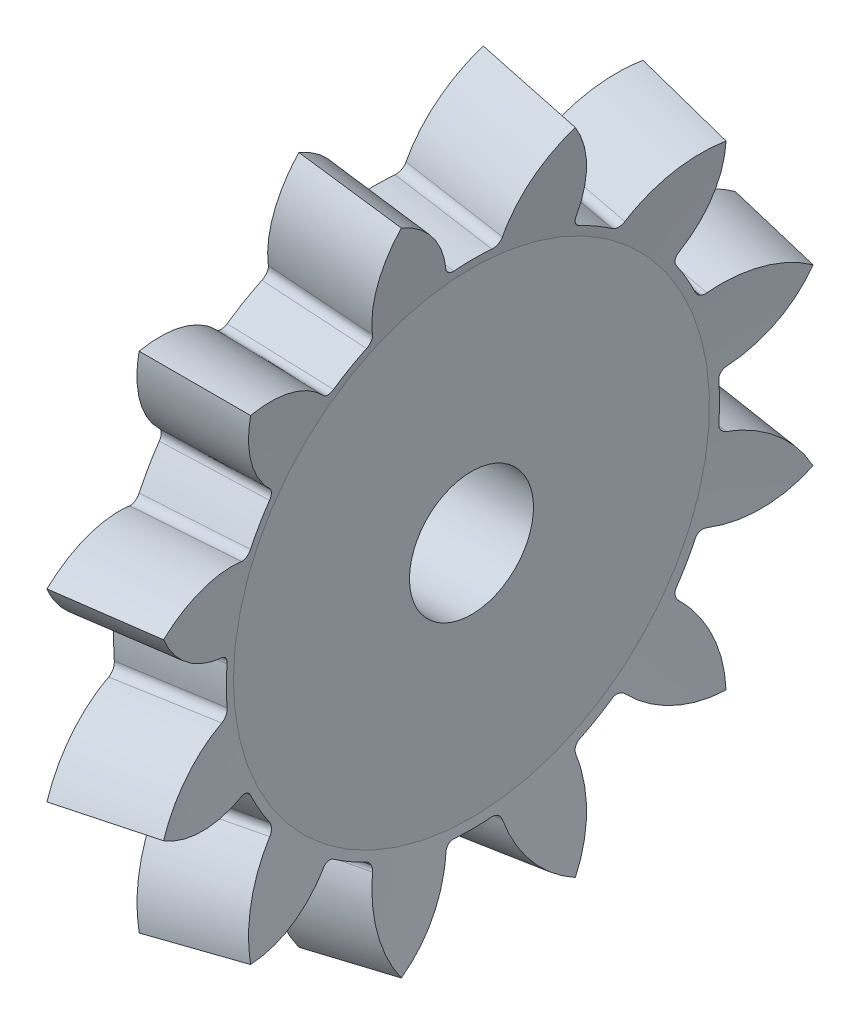
SolidWorks part; units mm, degrees
revolve "Base-Revolve" add sketch "BasProSke" angle 360 about L0 other way angle 15
sketch "BasProSke" plane through (0, 0, 0) normal (0, 1, 0) x (1, 0, 0)
  line L0 (-10, 0) -> (60, 0) construction
  line L1 (0, 0) -> (0, 10.1716)
  line L2 (0, 0) -> (3.9601, 0)
  line L3 (3.9601, 0) -> (3.9601, 9.5987)
  line L4 (70.3134, 0) -> (-30.9402, 17.3578) construction
  line L5 (0, 10.1716) -> (0.8022, 14.8514)
  line L6 (70.3134, 0) -> (-53.9726, 26.5543) construction
  line L7 (70.3134, 0) -> (0, 10.1716) construction
  line L8 (0.8022, 14.8514) -> (4.7172, 14.0149)
  line L9 (4.7172, 14.0149) -> (3.9601, 9.5987)
  line L10 (0.3134, 12) -> (-11.6709, 12) construction
  dimension "Addendum" = 2.893
  dimension "Pitch_rad" = 12
  dimension "Dedendum_plus" = 1.855
  dimension "Face_wid" = 4
  dimension "Pitch_ang" = 9.728
  dimension "D1" = 20.3433
  dimension "D2" = 70.3134
  dimension "D3" = 71.0211
  dimension "D4" = 2.333
ref_plane "Plane1" through (0, 0, 0) normal (0, 0, 1) x (1, 0, 0)
ref_plane "Plane2" through (0, 0, 0) normal (0, 1, 0) x (1, 0, 0)
ref_plane "Plane3" through (0, 0, 0) normal (1, 0, 0) x (0, 0, -1)
sketch "HoldingSke" plane through (0, 0, 0) normal (0, 1, 0) x (1, 0, 0)
  line L0 (0, 0) -> (0.4891, -0.104)
  line L1 (-15, 0) -> (100, 0) construction
  line L2 (0, 0) -> (20.372, 93.3937)
  line L3 (0, 0) -> (-11.863, 4.5341)
  line L4 (0, 0) -> (8.4473, 1.7955)
  line L5 (0, 0) -> (-9.3695, -3.4946)
  line L6 (0, 0) -> (-10.5278, -7.1032)
  line L7 (20.372, 93.3937) -> (80.2793, 130.2054)
  line L8 (-76.2, 2) -> (-75.3, 2)
  line L9 (-71.009, 38.7566) -> (-53.1078, 45.2721)
  line L10 (-76.2, 71.12) -> (104.1128, 71.12)
  line L11 (0, 0) -> (-4, 0)
  line L12 (-76.2, 101.6) -> (-76.133, 101.6)
  line L13 (24.9733, 27.94) -> (52.9472, 28.6464)
  line L14 (24.9733, 27.94) -> (24.9743, 27.94)
  line L15 (24.9733, 27.94) -> (100.4123, 28.9164)
  line L16 (20.372, 93.3937) -> (64.5293, -27.9275)
  circle A0 centre (0, 0) radius 2.5
  circle A1 centre (0, 0) radius 2.5
  circle A2 centre (0, 0) radius 2.5
  circle A3 centre (0, 0) radius 2.5
  dimension "MHD" = 5
  dimension "Hub_dia" = 5
  dimension "Bore" = 5
  dimension "MBD" = 5
  dimension "Num_teeth" = 12
  dimension "Pitch" = 0.5
  dimension "Mounting_dist" = 10
  dimension "Show_teeth" = 12
  dimension "Thickness" = 12.7
  dimension "OAL" = 70.3135
  dimension "T_dim" = 0.9
  dimension "Ap" = 20
  dimension "H" = 19.05
  dimension "Pitch_radius" = 180.3128
  dimension "Width" = 4
  dimension "Backlash" = 0.067
  dimension "Addendum_fac" = 1.446
  dimension "Dedendum_fac" = 0.742
  dimension "Clearance_fac" = 0.188
  dimension "Dedendum_add" = 0.001
  dimension "Mating_teeth" = 70
  dimension "MnMD" = 70.3134
  dimension "Module" = 2
ref_plane "ToothPln" through (0.4011, 12.5115, 0) normal (-0.9856, 0.169, 0) x (0, 0, -1)
ref_plane "ToothPln2" through (68.3061, -11.7096, 0) normal (-0.9856, 0.169, 0) x (0, 0, 1)
sketch "TooCutSke" plane through (0.4011, 12.5115, 0) normal (-0.9856, 0.169, 0) x (0, 0, -1)
  line L2 (0, 12.519) -> (431.6758, -1598.5171) construction
  line L3 (0, 12.519) -> (236.3419, -1744.44) construction
  line L4 (0, -15.621) -> (0, 105.791) construction
  line L6 (-24.765, -2.374) -> (21.082, -2.374) construction
  line L7 (3.1058, 0.9278) -> (1.5867, 0.7235) construction
  arc A0 (-4.9917, -1.8283) -> (4.9917, -1.8283) centre (0, 12.519) ccw
  arc A1 (-0.8122, 2.0344) -> (0.8122, 2.0344) centre (0, 12.519) ccw
  circle A2 centre (0, 12.519) radius 12 construction
  circle A3 centre (0, 12.519) radius 11.2763 construction
  arc A4 (1.2075, 1.7483) -> (0.8122, 2.0344) centre (0.8414, 1.6585) ccw
  arc A5 (1.2075, 1.7483) -> (4.9917, -1.8283) centre (5.8696, 2.8907) ccw
  arc A6 (-4.9917, -1.8283) -> (-1.2075, 1.7483) centre (-5.8696, 2.8907) ccw
  arc A7 (-0.8122, 2.0344) -> (-1.2075, 1.7483) centre (-0.8414, 1.6585) ccw
  ellipse E0 centre (0, 12.2638) end of major axis (14.8514, 12.2638) minor radius 14.6378 construction
sketch "TooCutSke2" plane through (68.3061, -11.7096, 0) normal (-0.9856, 0.169, 0) x (0, 0, 1)
  line L0 (0, 0) -> (0, 68.072) construction
  line L2 (21.082, 10.0254) -> (-20.32, 10.0254) construction
  circle A0 centre (0, 11.8804) radius 0.0127
  ellipse E1 centre (0, 0) end of major axis (-10.1716, 0) minor radius 10.0254 construction
  dimension "Dedendum_plus" = 1.855
loft "ToothCut" cut profiles "TooCutSke2", "TooCutSke"
pattern_circular "TeethCuts" count 12 every 30 about axis through (-10, 0, 0) along (1, 0, 0) of "ToothCut"
sketch "HubSke" plane through (0, 0, 0) normal (-1, 0, 0) x (0, 0, 1)
  circle A0 centre (0, 0) radius 2.5
  dimension "Diameter" = 5
extrude "Hub" add sketch "HubSke" along normal blind 0.0001
sketch "BorSke" plane through (0, 0, 0) normal (1, 0, 0) x (0, 0, -1)
  circle A0 centre (0, 0) radius 2.5
  dimension "Diameter" = 5
extrude "Bore" cut sketch "BorSke" along normal mid plane 140.627
sketch "KeySke" plane through (0, 0, 0) normal (1, 0, 0) x (0, 0, -1)
  line L0 (-1, 0) -> (-1, 3.4)
  line L1 (-1, 3.4) -> (1, 3.4)
  line L2 (1, 3.4) -> (1, 0)
  line L3 (0, 0) -> (0, 34) construction
  line L4 (-1, 0) -> (1, 0)
  dimension "Offset" = 3.4
extrude "Keyway" [suppressed] cut sketch "KeySke" along normal mid plane 140.627
pattern_circular "Keyway2" [suppressed] count 2 every 90 about axis through (-10, 0, 0) along (1, 0, 0) reverse direction yes
equation "' \"Module@HoldingSke\" = 6.35"
equation "' \"Num_teeth@HoldingSke\" = 12"
equation "' \"Mating_teeth@HoldingSke\" = 20"
equation "' \"Ap@HoldingSke\" =  20"
equation "' \"Ap@HoldingSke\" = 20"
equation "' \"Width@HoldingSke\" = 0.5 * 25.4"
equation "' \"Hub_dia@HoldingSke\"= 2 * 25.4"
equation "' \"Hub_dia@HoldingSke\" = 2 * 25.4"
equation "' \"Mounting_dist@HoldingSke\" = 3 * 25.4"
equation "' \"Bore@HoldingSke\" = 19"
equation "' \"T_dim@HoldingSke\" = 0.1 * 25.4"
equation "' \"Width@KeySke\" = 0.25 * 25.4"
equation "' \"Show_teeth@HoldingSke\" = 100"
equation "' \"Backlash@HoldingSke\" = 0.009 * 25.4"
equation "' \"Addendum_fac@HoldingSke\" = 1.0"
equation "' \"Dedendum_fac@HoldingSke\" = 1.188"
equation "' \"Dedendum_add@HoldingSke\" = 0.002 * 25.4"
equation "' \"Clearance_fac@HoldingSke\" = 0.188"
equation "\"Pitch@HoldingSke\" = 1 / \"Module@HoldingSke\""
equation "' \"Addendum_fac@HoldingSke\" = 0.54 + 0.46 / (\"Num_teeth@HoldingSke\" /  \"Mating_teeth@HoldingSke\" ) ^ 2"
equation " \"Addendum_fac@HoldingSke\" = 2 - (0.54 + 0.46 / (\"Mating_teeth@HoldingSke\" /  \"Num_teeth@HoldingSke\" ) ^ 2)"
equation "\"Dedendum_fac@HoldingSke\" = 2.188 - \"Addendum_fac@HoldingSke\""
equation "\"Pitch_rad@BasProSke\" = \"Num_teeth@HoldingSke\" / \"Pitch@HoldingSke\" / 2"
equation "\"Pitch_ang@BasProSke\" = atn(\"Num_teeth@HoldingSke\" / \"Mating_teeth@HoldingSke\") * (180 / 3.14159265)"
equation "\"Addendum@BasProSke\" = \"Addendum_fac@HoldingSke\" / \"Pitch@HoldingSke\""
equation "\"Dedendum_plus@BasProSke\" = (\"Dedendum_fac@HoldingSke\" / \"Pitch@HoldingSke\" + \"Dedendum_add@HoldingSke\") * 1.25"
equation "\"Face_wid@BasProSke\" = \"Width@HoldingSke\""
equation "\"Radius@TooCutSke\" = ((\"Num_teeth@HoldingSke\" + 2 * \"Addendum_fac@HoldingSke\") / \"Pitch@HoldingSke\" ) / 2"
equation "\"Overcut_dia@TooCutSke\" =  1.02 * (\"Num_teeth@HoldingSke\" + 2 * \"Addendum_fac@HoldingSke\") / \"Pitch@HoldingSke\""
equation "\"Pitch_dia@TooCutSke\" = \"Num_teeth@HoldingSke\" / \"Pitch@HoldingSke\""
equation "\"Base_dia@TooCutSke\" = \"Num_teeth@HoldingSke\" / \"Pitch@HoldingSke\" * cos((\"Ap@HoldingSke\"  * 3.14159265 / 180))"
equation "'  \"Root_dia@TooCutSke\" =  (\"Num_teeth@HoldingSke\" + 2) / \"Pitch@HoldingSke\" - 2 * (\"Addendum_fac@HoldingSke\" + \"Dedendum_fac@HoldingSke\") / \"Pitch@HoldingSke\" - \"Dedendum_add@HoldingSke\" * 2"
equation "'  \"Root_dia@TooCutSke\" = (\"Num_teeth@HoldingSke\" + 2) / \"Pitch@HoldingSke\" - 2 * (\"Addendum_fac@HoldingSke\" + \"Dedendum_fac@HoldingSke\") / \"Pitch@HoldingSke\" - \"Dedendum_add@HoldingSke\" * 2"
equation "\"Root_dia@TooCutSke\" =  \"Num_teeth@HoldingSke\" / \"Pitch@HoldingSke\" -  2 * \"Dedendum_fac@HoldingSke\" / \"Pitch@HoldingSke\" - \"Dedendum_add@HoldingSke\" * 2"
equation "\"Half_ang@TooCutSke\" = 180 / \"Num_teeth@HoldingSke\""
equation "\"Half_CT@TooCutSke\" = \"Num_teeth@HoldingSke\" / \"Pitch@HoldingSke\" * sin((3.14159265 / 2 / \"Num_teeth@HoldingSke\")) / 2 - 2 * \"Backlash@HoldingSke\" / 4"
equation "\"Flank_rad@TooCutSke\" = \"Num_teeth@HoldingSke\" / \"Pitch@HoldingSke\" / 5"
equation "\"Root_fillet@TooCutSke\" = \"Clearance_fac@HoldingSke\" / \"Pitch@HoldingSke\" + \"Dedendum_add@HoldingSke\""
equation "\"Offset@ToothPln2\"  = \"Num_teeth@HoldingSke\" / \"Pitch@HoldingSke\" / 2 / sin(atn(\"Num_teeth@HoldingSke\" / \"Mating_teeth@HoldingSke\"))"
equation "\"Dedendum_plus@TooCutSke2\" = \"Dedendum_plus@BasProSke\""
equation "\"MHD@HoldingSke\" = \"Num_teeth@HoldingSke\" / \"Pitch@HoldingSke\" - 2 * \"Dedendum_plus@BasProSke\" * cos(atn(\"Num_teeth@HoldingSke\" / \"Mating_teeth@HoldingSke\"))"
equation "\"MBD@HoldingSke\" = \"Num_teeth@HoldingSke\" / \"Pitch@HoldingSke\" - 2 * \"Dedendum_plus@BasProSke\" * cos(atn(\"Num_teeth@HoldingSke\" / \"Mating_teeth@HoldingSke\")) - 0.002 * 25.4"
equation "\"MnMD@HoldingSke\" =  \"Num_teeth@HoldingSke\" / \"Pitch@HoldingSke\" / 2 / (\"Num_teeth@HoldingSke\" / \"Mating_teeth@HoldingSke\") + \"Dedendum_plus@BasProSke\" * sin(atn(\"Num_teeth@HoldingSke\" / \"Mating_teeth@HoldingSke\"))"
equation "\"OAL@HoldingSke\" = \"MnMD@HoldingSke\""
equation "\"MHD@HoldingSke\" = ((sgn( \"MHD@HoldingSke\" - \"Hub_dia@HoldingSke\" )-1)*( \"MHD@HoldingSke\" - \"Hub_dia@HoldingSke\" ))/-2+ \"Hub_dia@HoldingSke\""
equation "\"MBD@HoldingSke\" = ((sgn( \"MBD@HoldingSke\" - \"Bore@HoldingSke\" )-1)*( \"MBD@HoldingSke\" - \"Bore@HoldingSke\" ))/-2+ \"Bore@HoldingSke\""
equation "\"Face_wid@BasProSke\" = ((sgn( \"Face_wid@BasProSke\" - \"Offset@ToothPln2\" * 0.9)-1)*( \"Face_wid@BasProSke\" - \"Offset@ToothPln2\" * 0.9))/-2+ \"Offset@ToothPln2\" * 0.9"
equation "\"OAL@HoldingSke\" = ((sgn( \"OAL@HoldingSke\" - \"Mounting_dist@HoldingSke\" )+1)*( \"OAL@HoldingSke\" - \"Mounting_dist@HoldingSke\" ))/2 + \"Mounting_dist@HoldingSke\" + 0.000002 * 25.4"
equation "\"Num_teeth@TeethCuts\" = int( \"Show_teeth@HoldingSke\" ) + 1"
equation "\"Num_teeth@TeethCuts\" = ((sgn( \"Num_teeth@TeethCuts\" - \"Num_teeth@HoldingSke\" )-1)*( \"Num_teeth@TeethCuts\" - \"Num_teeth@HoldingSke\" ))/-2+ \"Num_teeth@HoldingSke\""
equation "\"Num_teeth@TeethCuts\" = ((sgn( \"Num_teeth@TeethCuts\" - 2.0)+1)*( \"Num_teeth@TeethCuts\" - 2.0))/2 +2.0"
equation "\"Angle@TeethCuts\" = 360.0 / \"Num_teeth@HoldingSke\""
equation "\"Diameter@HubSke\" = \"MHD@HoldingSke\""
equation "\"Length@Hub\" = \"OAL@HoldingSke\" - \"MnMD@HoldingSke\" + 0.000002 * 25.4"
equation "\"Diameter@BorSke\" = \"MBD@HoldingSke\""
equation "\"D1@Bore\" = \"OAL@HoldingSke\" * 2.0"
equation "\"D1@Keyway\" = \"OAL@HoldingSke\" * 2.0"
equation "\"Offset@KeySke\" = \"T_dim@HoldingSke\" + \"MBD@HoldingSke\" / 2.0"
